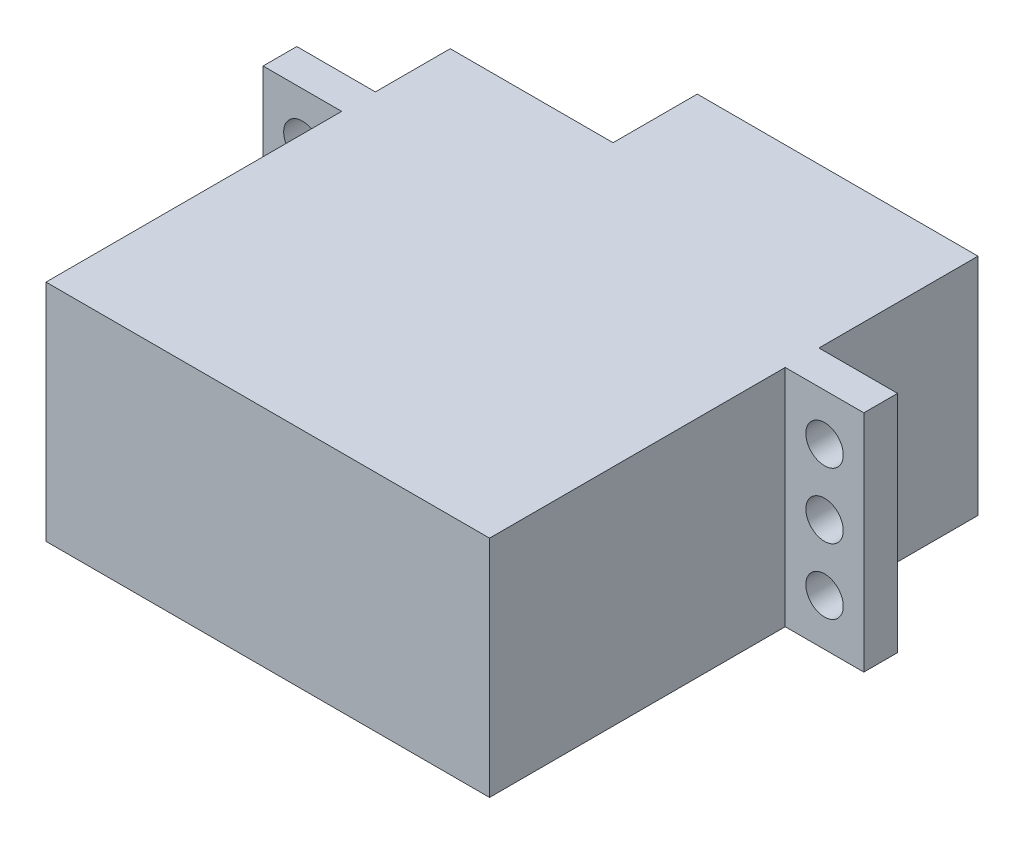
SolidWorks part; units mm, degrees
ref_plane "Front Plane" through (0, 0, 0) normal (0, 0, 1) x (1, 0, 0)
ref_plane "Top Plane" through (0, 0, 0) normal (0, 1, 0) x (1, 0, 0)
ref_plane "Right Plane" through (0, 0, 0) normal (1, 0, 0) x (0, 0, -1)
sketch "Sketch1" plane through (0, 0, 0) normal (0, 0, 1) x (1, 0, 0)
  line L1 (0, 0) -> (23.7, 0)
  line L2 (0, 0) -> (0, -12)
  line L3 (0, -12) -> (23.7, -12)
  line L4 (23.7, 0) -> (23.7, -12)
  dimension "D1" = 23.7
  dimension "D2" = 12
extrude "Boss-Extrude1" add sketch "Sketch1" along normal blind 21.6
ref_plane "Plane1" through (0, 0, 4) normal (0, 0, -1) x (-1, 0, 0)
sketch "Sketch2" plane through (0, 0, 4) normal (0, 0, -1) x (-1, 0, 0)
  line L0 (0, -12) -> (-23.7, -12) construction
  line L1 (4.2, 0) -> (-27.9, 0)
  line L2 (4.2, 0) -> (4.2, -12)
  line L3 (4.2, -12) -> (-27.9, -12)
  line L4 (-27.9, 0) -> (-27.9, -12)
  line L5 (-23.7, 0) -> (0, 0) construction
  line L6 (0, 0) -> (0, -12) construction
  line L7 (-23.7, -12) -> (-23.7, 0) construction
  line L8 (1.1, -2.5) -> (4.2, -2.5) construction
  line L9 (3.1, -2.5) -> (0, -2.5) construction
  line L10 (2.1, -1.5) -> (2.1, 0) construction
  line L11 (-24.8, -2.5) -> (-27.9, -2.5) construction
  line L12 (2.1, -3.5) -> (2.1, -5) construction
  circle A0 centre (2.1, -2.5) radius 1
  circle A1 centre (-25.8, -2.5) radius 1
  circle A2 centre (-25.8, -6) radius 1
  circle A3 centre (-25.8, -9.5) radius 1
  circle A4 centre (2.1, -6) radius 1
  circle A5 centre (2.1, -9.5) radius 1
  dimension "D3" = 2
  dimension "D1" = 4.2
  dimension "D2" = 4.2
  dimension "D4" = 1.5
  dimension "D5" = 2
  dimension "D7" = 1.5
  dimension "D6" = 3
extrude "Boss-Extrude2" add sketch "Sketch2" against normal blind 1.8
sketch "Sketch3" plane through (0, 0, 0) normal (0, 0, -1) x (-1, 0, 0)
  line L0 (0, -12) -> (-23.7, -12) construction
  line L1 (-23.7, 0) -> (-8.7, 0)
  line L2 (-23.7, 0) -> (-23.7, -12)
  line L3 (-23.7, -12) -> (-8.7, -12)
  line L4 (-8.7, 0) -> (-8.7, -12)
  dimension "D1" = 15
extrude "Boss-Extrude3" add sketch "Sketch3" along normal blind 4.5
sketch "Sketch4" plane through (0, 0, -4.5) normal (0, 0, -1) x (-1, 0, 0)
  line L0 (-23.7, -12) -> (-23.7, 0) construction
  line L1 (-16.7, -3.6) -> (-16.7, 0) construction
  line L3 (-16.7, -8.4) -> (-16.7, -12) construction
  line L4 (-23.7, -12) -> (-8.7, -12) construction
  line L5 (-8.7, 0) -> (-23.7, 0) construction
  circle A0 centre (-16.7, -6) radius 2.4
  dimension "D1" = 4.8
  dimension "D2" = 7
extrude "Boss-Extrude4" add sketch "Sketch4" along normal blind 3.2
